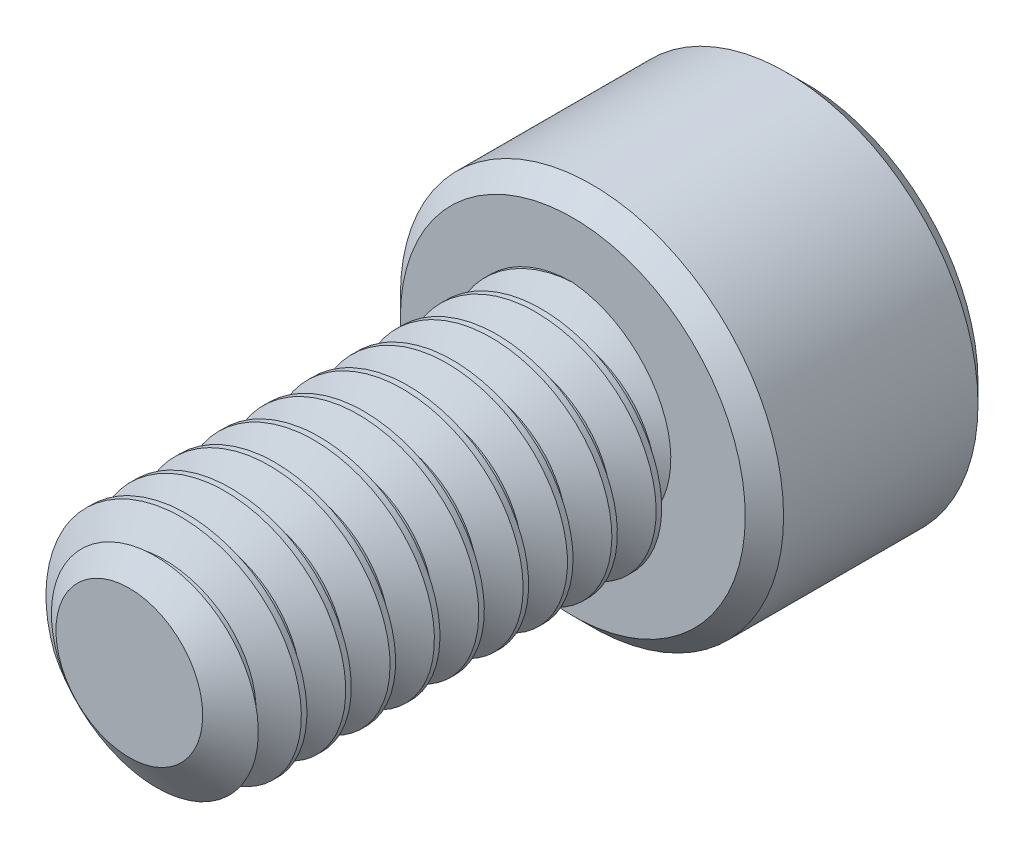
SolidWorks part; units mm, degrees
ref_plane "Front Plane" through (0, 0, 0) normal (0, 0, 1) x (1, 0, 0)
ref_plane "Top Plane" through (0, 0, 0) normal (0, 1, 0) x (1, 0, 0)
ref_plane "Right Plane" through (0, 0, 0) normal (1, 0, 0) x (0, 0, -1)
sketch "Sketch1" plane through (0, 0, 0) normal (0, 0, 1) x (1, 0, 0)
  circle A0 centre (0, 0) radius 2.0828
  dimension "OD" = 4.1656
extrude "Extrude1" add sketch "Sketch1" against normal blind 7.9375
sketch "Sketch2" plane through (0, 0, 0) normal (0, 0, 1) x (1, 0, 0)
  circle A0 centre (0, 0) radius 2.0828 construction
  circle A1 centre (0, 0) radius 2.0828
curve "Helix/Spiral1" pitch 0.7937 height 8.7312 turns 11 parameters "pitch"=0.7937
sketch "Sketch3" plane through (0, 0, 0) normal (1, 0, 0) x (0, 0, -1)
  line L0 (-0.6945, 2.0828) -> (-0.3969, 1.5672)
  line L1 (-0.3969, 1.5672) -> (-0.2977, 1.5672)
  line L2 (-0.2977, 1.5672) -> (0, 2.0828)
  line L3 (-0.6945, 2.0828) -> (0, 2.0828)
  line L4 (-0.3473, 2.0828) -> (-0.3473, 1.5672) construction
  line L5 (-0.5457, 1.825) -> (-0.1488, 1.825) construction
  line L6 (0, 2.0828) -> (0, -2.0828) construction
  dimension "D1" = 0.0992
  dimension "D2" = 0.3969
  dimension "D3" = 60
sweep "Cut-Sweep1" cut profiles "Sketch3" path "Helix/Spiral1"
sketch "Sketch4" plane through (0, 0, 0) normal (1, 0, 0) x (0, 0, -1)
  line L0 (0.5388, 2.0828) -> (0, 1.3132)
  line L1 (0, 1.3132) -> (0, 2.0828)
  line L2 (0.5388, 2.0828) -> (0, 2.0828)
  line L3 (-0.6945, 2.0828) -> (0, 2.0828) construction
  line L4 (0, 0) -> (7.0209, 0) construction
  dimension "D1" = 55
  dimension "D2" = 0.254
revolve "Cut-Revolve1" cut sketch "Sketch4" angle 360 about L4
sketch "Sketch5" plane through (0, 0, 0) normal (1, 0, 0) x (0, 0, -1)
  line L0 (7.9375, -1.5805) -> (7.9375, 1.4861) construction
  line L1 (7.9375, 2.2098) -> (87.4327, 2.2098)
  line L2 (7.9375, 2.2098) -> (7.9375, 0)
  line L3 (7.9375, 0) -> (87.3125, 0)
  line L4 (87.3125, 1.8796) -> (87.3125, 0)
  line L5 (87.4327, 2.2098) -> (87.3125, 1.8796)
  line L6 (0, 0) -> (9.9695, 0) construction
  point P3 (87.3125, 2.2098)
  point P10 (87.3125, 2.2098)
  dimension "D1" = 0.3302
  dimension "Thread min" = 87.3125
  dimension "D2" = 0.127
  dimension "D3" = 20
revolve "partially thread" [suppressed] add sketch "Sketch5" angle 360 about L6
sketch "Sketch6" plane through (0, 0, -7.9375) normal (0, 0, -1) x (-1, 0, 0)
  circle A0 centre (0, 0) radius 3.429
  dimension "head dia" = 6.858
extrude "Extrude2" add sketch "Sketch6" along normal blind 4.1656
sketch "Sketch7" plane through (0, 0, -12.1031) normal (0, 0, -1) x (-1, 0, 0)
  line L1 (0, 2.0622) -> (-1.7859, 1.0311)
  line L2 (-1.7859, 1.0311) -> (-1.7859, -1.0311)
  line L3 (-1.7859, -1.0311) -> (0, -2.0622)
  line L4 (0, -2.0622) -> (1.7859, -1.0311)
  line L5 (1.7859, -1.0311) -> (1.7859, 1.0311)
  line L6 (1.7859, 1.0311) -> (0, 2.0622)
  circle A0 centre (0, 0) radius 1.7859 construction
  dimension "hex dia" = 3.5719
extrude "Cut-Extrude1" cut sketch "Sketch7" against normal blind 2.6789
sketch "Sketch8" plane through (0, 0, -12.1031) normal (0, 0, -1) x (-1, 0, 0)
  circle A0 centre (0, 0) radius 2.0622
extrude "Cut-Extrude2" cut sketch "Sketch8" against normal through all draft 45
chamfer "Chamfer1" distance 0.3429 angle 45 2 edges at (-3.429, 0, -12.1031) (-3.429, 0, -7.9375)
sketch "Sketch9" plane through (0, 0, 0) normal (1, 0, 0) x (0, 0, -1)
  line L0 (0, 2.0828) -> (0, -2.0828) construction
  line L1 (4.3656, 2.0828) -> (4.3656, -2.0828) construction
  dimension "D1" = 4.3656
  dimension "D4" = 0.635
  dimension "D5" = 0.3302
equation "\"D3@Helix/Spiral1\" = \"screw length@Extrude1\"+\"pitch@Helix/Spiral1\""
equation "\"D1@Sketch3\" = \"pitch@Helix/Spiral1\"*.125"
equation "\"D2@Sketch3\" = \"pitch@Helix/Spiral1\"*.5"
equation "\"D1@Cut-Extrude1\" = \"hex dia@Sketch7\"*.75"
equation "\"D1@Chamfer1\" = \"head dia@Sketch6\"*.05"
equation "\"D1@Sketch9\" = \"pitch@Helix/Spiral1\"*5.5"
